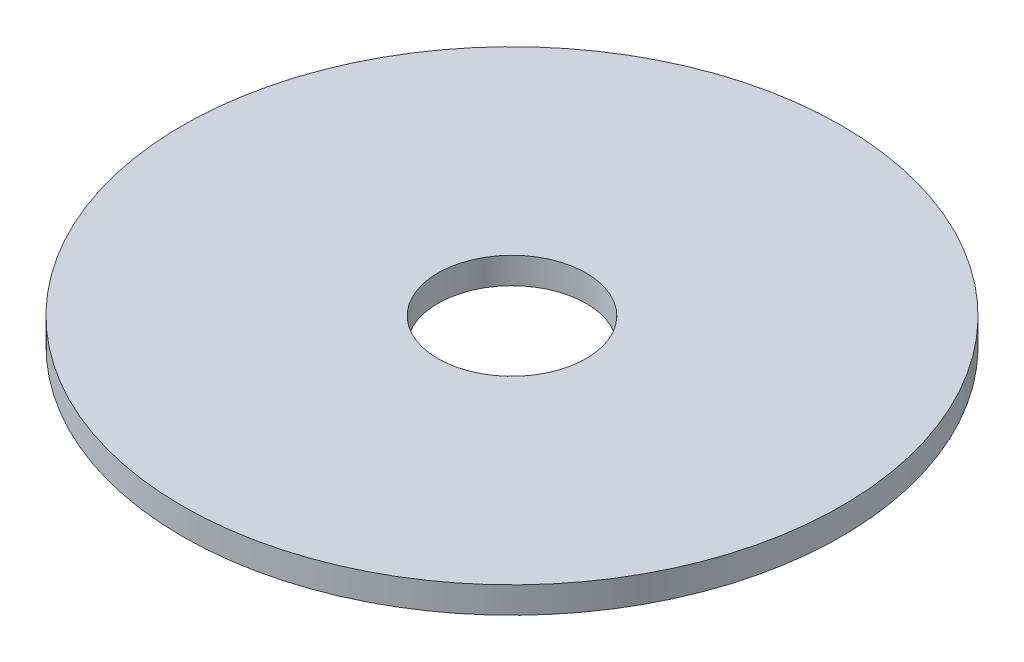
SolidWorks part; units mm, degrees
ref_plane "Front Plane" through (0, 0, 0) normal (0, 0, 1) x (1, 0, 0)
ref_plane "Top Plane" through (0, 0, 0) normal (0, 1, 0) x (1, 0, 0)
ref_plane "Right Plane" through (0, 0, 0) normal (1, 0, 0) x (0, 0, -1)
sketch "Sketch1" plane through (0, 0, 0) normal (0, 1, 0) x (1, 0, 0)
  circle A0 centre (0, 0) radius 100
  dimension "FLANGE_OD" = 200
extrude "Boss-Extrude1" add sketch "Sketch1" along normal blind 8
sketch "Sketch2" plane through (0, 0, 0) normal (0, 1, 0) x (1, 0, 0)
  circle A0 centre (0, 0) radius 22.5
  dimension "BORE_D" = 45
extrude "Cut-Extrude1" cut sketch "Sketch2" along normal through all
sketch "Sketch3" plane through (0, 8, 0) normal (0, 1, 0) x (1, 0, 0)
  circle A0 centre (0, 0) radius 14.646 construction
  circle A1 centre (-14.646, 0) radius 5.266
  dimension "BOLT_D" = 10.5319
  dimension "BOLT_PCD" = 29.2921
extrude "Cut-Extrude2" cut sketch "Sketch3" against normal blind 6.5718 rebuild error yes
pattern_circular "CirPattern1" count 5 over 360 rebuild error yes
